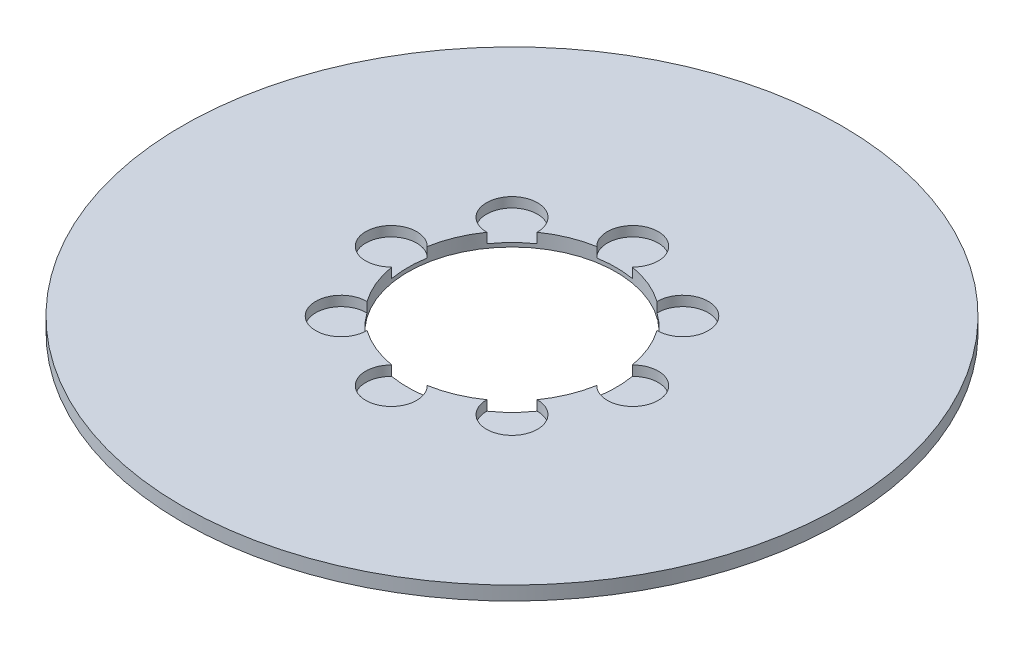
SolidWorks part; units mm, degrees
ref_plane "Front Plane" through (0, 0, 0) normal (0, 0, 1) x (1, 0, 0)
ref_plane "Top Plane" through (0, 0, 0) normal (0, 1, 0) x (1, 0, 0)
ref_plane "Right Plane" through (0, 0, 0) normal (1, 0, 0) x (0, 0, -1)
sketch "Sketch1" plane through (0, 0, 0) normal (0, 1, 0) x (1, 0, 0)
  circle A0 centre (0, 0) radius 95
  dimension "FLANGE_OD" = 190
extrude "Boss-Extrude1" add sketch "Sketch1" along normal blind 4
sketch "Sketch2" plane through (0, 0, 0) normal (0, 1, 0) x (1, 0, 0)
  circle A0 centre (0, 0) radius 30
  dimension "BORE_D" = 60
extrude "Cut-Extrude1" cut sketch "Sketch2" along normal through all
sketch "Sketch3" plane through (0, 4, 0) normal (0, 1, 0) x (1, 0, 0)
  circle A0 centre (0, 0) radius 34.8176 construction
  circle A1 centre (-34.8176, 0) radius 7.3355
  dimension "BOLT_D" = 14.671
  dimension "BOLT_PCD" = 69.6351
extrude "Cut-Extrude2" cut sketch "Sketch3" against normal blind 2.861
pattern_circular "CirPattern1" count 8 over 360 about axis through (0, 0, 0) along (0, 1, 0) of "Cut-Extrude2"
